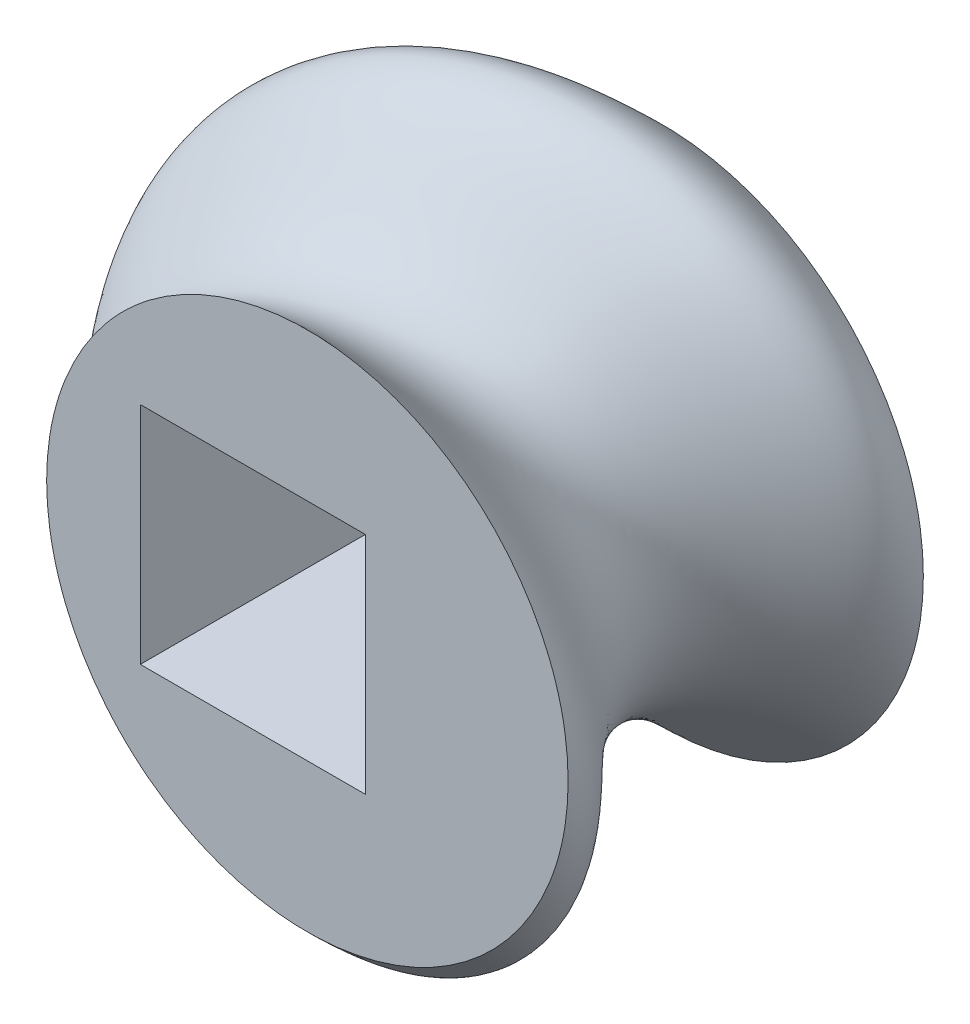
SolidWorks part; units mm, degrees
ref_plane "Ebene vorne" through (0, 0, 0) normal (0, 0, 1) x (1, 0, 0)
ref_plane "Ebene oben" through (0, 0, 0) normal (0, 1, 0) x (1, 0, 0)
ref_plane "Ebene rechts" through (0, 0, 0) normal (1, 0, 0) x (0, 0, -1)
sketch "Skizze2" plane through (0, 0, 0) normal (0, 0, 1) x (1, 0, 0)
  circle A0 centre (0, 0) radius 14.681
  dimension "D1" = 29.362
ref_plane "Ebene1" through (0, 0, 0) normal (0, 0, 1) x (1, 0, 0)
sketch "Skizze3" plane through (0, 0, 0) normal (0, 0, 1) x (1, 0, 0)
  circle A0 centre (-3.071, 0) radius 4
  point P0 (-3.071, 0)
  dimension "D2" = 8
  dimension "D1" = 3.071
curve "Spirale/Helix1" pitch 20 height 20 radius 4 centre (-3.071, 0, 0) axis (0, 0, 1) start towards (1, 0, 0)
sweep "Austragung1" add profiles "Skizze2" path "Spirale/Helix1"
sketch "Skizze5" plane through (0, 0, 20) normal (0, 0, 1) x (1, 0, 0)
  circle A0 centre (0, 0) radius 2.5
  dimension "D1" = 5
ref_plane "Ebene3" through (0.929, 0, 0) normal (0, 0.7825, 0.6227) x (1, 0, 0)
extrude "Schnitt-Linear austragen2" cut sketch "Skizze3<2>" along normal blind 27
sketch "Skizze3<2>" plane through (0, 0, 0) normal (0, 0, 1) x (1, 0, 0) same geometry as "Skizze3"
ref_axis "Achse2" through (-3.071, 0, 20) along (0, 0, -1)
sketch "Skizze7" plane through (0, 0, 0) normal (0, 0, 1) x (1, 0, 0)
  line L5 (-9.4064, 6.3354) -> (3.2644, -6.3354) construction
  line L6 (-9.4064, -6.3354) -> (3.2644, 6.3354) construction
  circle A0 centre (-3.071, 0) radius 8.9596
sketch "Skizze8" plane through (0, 0, 20) normal (0, 0, 1) x (1, 0, 0)
  line L1 (-9.4064, 6.3354) -> (3.2644, 6.3354)
  line L2 (-9.4064, 6.3354) -> (-9.4064, -6.3354)
  line L3 (-9.4064, -6.3354) -> (3.2644, -6.3354)
  line L4 (3.2644, 6.3354) -> (3.2644, -6.3354)
  line L5 (-9.4064, 6.3354) -> (3.2644, -6.3354) construction
  line L6 (-9.4064, -6.3354) -> (3.2644, 6.3354) construction
  point P0 (-3.071, 0)
extrude "Schnitt-Linear austragen3" cut sketch "Skizze8" against normal blind 25
